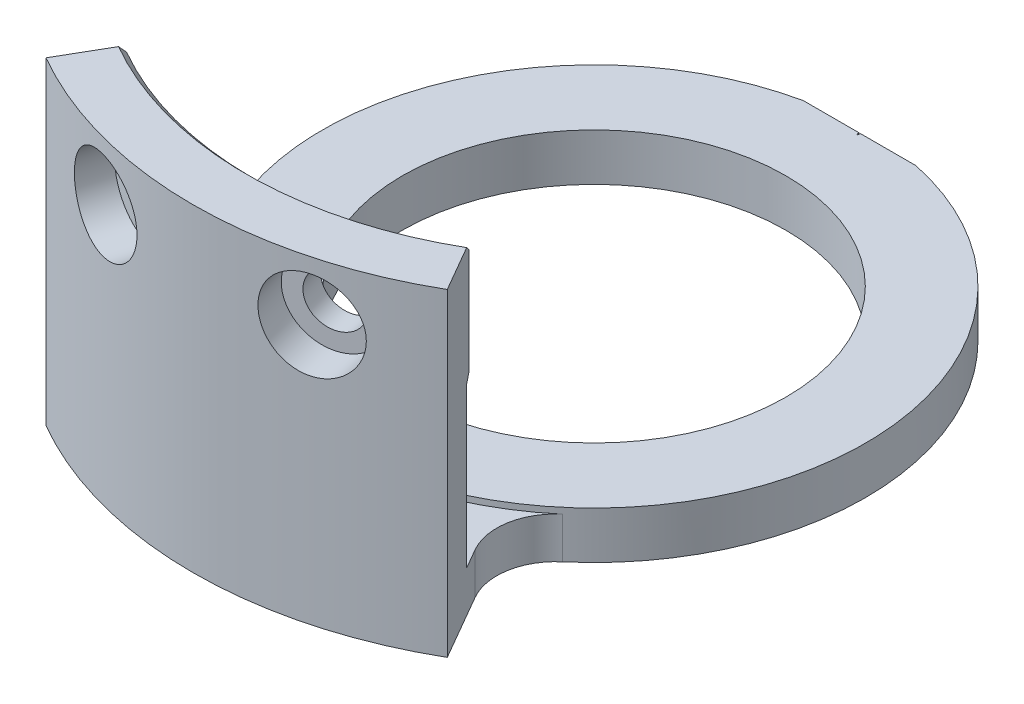
SolidWorks part; units mm, degrees
ref_plane "前视基准面" through (0, 0, 0) normal (0, 0, 1) x (1, 0, 0)
ref_plane "上视基准面" through (0, 0, 0) normal (0, 1, 0) x (1, 0, 0)
ref_plane "右视基准面" through (0, 0, 0) normal (1, 0, 0) x (0, 0, -1)
sketch "草图1" plane through (0, 0, 0) normal (0, 1, 0) x (1, 0, 0)
  circle A0 centre (0, 0) radius 23
  dimension "D1" = 46
extrude "凸台-拉伸1" add sketch "草图1" along normal blind 4
sketch "草图3" plane through (0, 4, 0) normal (0, 1, 0) x (1, 0, 0)
  line L0 (-4.7697, 22.5) -> (4.7697, 22.5)
  line L1 (-2.2, 0) -> (2.2, 0) construction
  circle A0 centre (0, 0) radius 23 construction
  dimension "D1" = 22.5
extrude "切除-拉伸1" cut sketch "草图3" against normal through all and the other way through all
sketch "草图4" plane through (0, 4, 0) normal (0, 1, 0) x (1, 0, 0)
  circle A0 centre (0, 0) radius 16.25
  dimension "D1" = 32.5
extrude "切除-拉伸2" cut sketch "草图4" against normal through all
sketch "草图5" plane through (0, 0, 0) normal (0, 1, 0) x (1, 0, 0)
  line L0 (0, 0) -> (-17, -29.4449)
  line L1 (0, 0) -> (17, -29.4449)
  circle A0 centre (0, 0) radius 34
  arc A1 (-4.7697, 22.5) -> (4.7697, 22.5) centre (0, 0) ccw construction
  arc A2 (-4.7697, 22.5) -> (4.7697, 22.5) centre (0, 0) ccw
  point P3 (0, 0)
  dimension "D1" = 68
  dimension "D2" = 60
extrude "凸台-拉伸2" add sketch "草图5" along normal blind 3.5 contours A2 L0 A0 L1 region at (0, 0, 27.5534)
fillet "圆角1" radius 5 2 edges at (-11.5, 1.75, 19.9186) (11.5, 1.75, 19.9186)
sketch "草图7" plane through (0, 3.5, 0) normal (0, 1, 0) x (1, 0, 0)
  line L0 (13.775, -23.859) -> (17, -29.4449) construction
  line L1 (-13.775, -23.859) -> (-17, -29.4449) construction
  line L2 (-14.5, -25.1147) -> (-17, -29.4449)
  line L3 (14.5, -25.1147) -> (17, -29.4449)
  arc A0 (-17, -29.4449) -> (17, -29.4449) centre (0, 0) ccw construction
  arc A1 (-17, -29.4449) -> (17, -29.4449) centre (0, 0) ccw
  arc A2 (14.5, -25.1147) -> (-14.5, -25.1147) centre (0, 0) cw
  dimension "D1" = 29
extrude "凸台-拉伸3" add sketch "草图7" along normal blind 27 from surface starting at face at (0, 0, 16.25)
sketch "草图8" plane through (0, 27, 0) normal (0, 1, 0) x (1, 0, 0)
  arc A2 (-14.75, -25.5477) -> (14.75, -25.5477) centre (0, 0) ccw
  arc A3 (-14.75, -25.5477) -> (14.75, -25.5477) centre (0, 0) ccw
  dimension "D1" = 0.5
extrude "切除-拉伸-薄壁1" cut sketch "草图8" against normal up to surface (23.5 mm away) from offset 10 thin up to face at (0, 3.5, 23.6633) offset against normal yes thin type one direction reverse wall 1
chamfer "倒角1" distance 0.5 angle 45 2 edges at (0, 17, 29) (0, 27, 29)
ref_plane "基准面1" through (0, 22, 0) normal (0, 1, 0) x (1, 0, 0)
sketch "草图9" plane through (0, 22, 0) normal (0, 1, 0) x (1, 0, 0)
  line L0 (0, 0) -> (-8.7998, -32.8415)
  line L1 (0, 0) -> (8.7998, -32.8415)
  arc A0 (-17, -29.4449) -> (17, -29.4449) centre (0, 0) ccw construction
  point P6 (0, 0)
  dimension "D1" = 30
hole_wizard "孔2" positions "3D草图3" profile "草图11" legacy
sketch3d "3D草图3"
  point P0 (8.7998, 22, 32.8415)
  point P2 (-8.7998, 22, 32.8415)
  point P6 (0, 0, 0)
sketch "草图11" plane through (8.7998, 22, 32.8415) normal (0, 1, 0) x (0.9659, 0, -0.2588)
  line L0 (0, 0) -> (0, 7.5)
  line L1 (0, 7.5) -> (2.25, 7.5)
  line L2 (2.25, 7.5) -> (2.25, 3)
  line L3 (2.25, 3) -> (3.75, 3)
  line L4 (3.75, 3) -> (3.75, 0)
  line L5 (3.75, 0) -> (0, 0)
  line L6 (0, 110) -> (0, -10) construction
  dimension "直径" = 4.5
  dimension "深度" = 7.5
  dimension "柱坑直径" = 7.5
  dimension "柱坑深度" = 3
sketch "草图12" plane through (0, 0, -22.5) normal (0, 0, -1) x (-1, 0, 0)
  line L0 (0, 4) -> (0, 1)
  line L1 (-4.7697, 4) -> (4.7697, 4) construction
  dimension "D1" = 3
extrude "切除-拉伸-薄壁2" cut sketch "草图12" against normal blind 0.2 thin thin type mid plane wall 0.1
